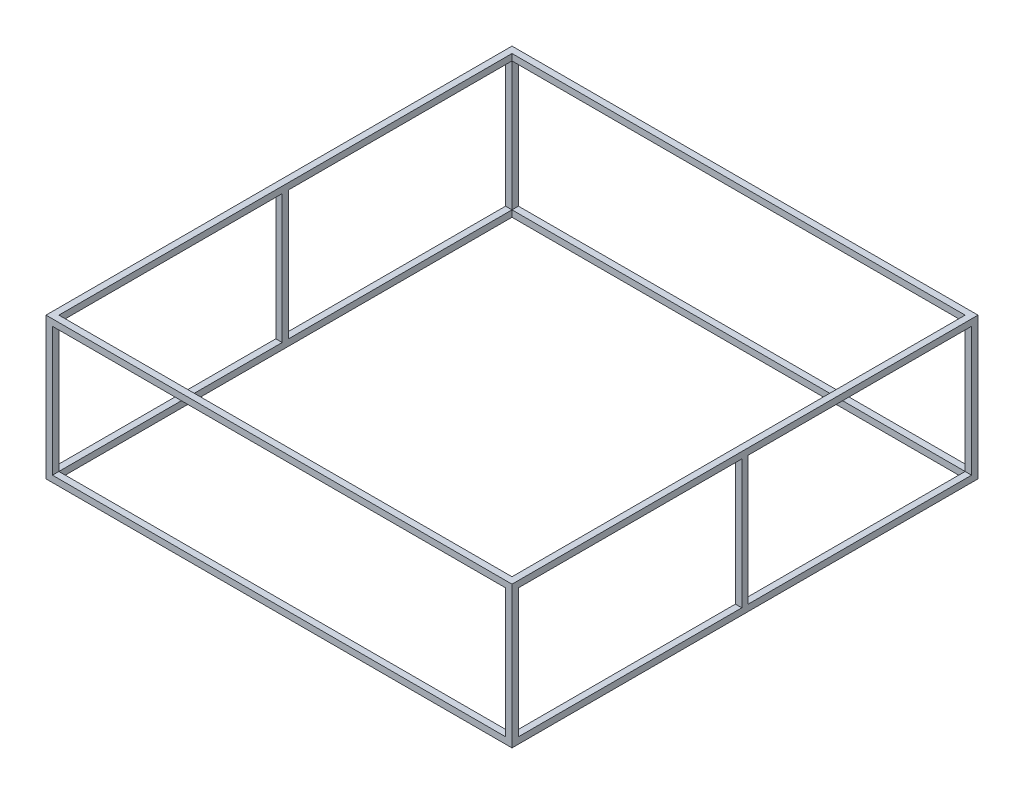
SolidWorks part; units mm, degrees
ref_plane "Front Plane" through (0, 0, 0) normal (0, 0, 1) x (1, 0, 0)
ref_plane "Top Plane" through (0, 0, 0) normal (0, 1, 0) x (1, 0, 0)
ref_plane "Right Plane" through (0, 0, 0) normal (1, 0, 0) x (0, 0, -1)
sketch "Sketch1" plane through (0, 0, 0) normal (0, 1, 0) x (1, 0, 0)
  line L0 (-559.125, 559.125) -> (-559.125, -559.125)
  line L1 (-575, 575) -> (575, 575)
  line L2 (-575, 575) -> (-575, -575)
  line L3 (-575, -575) -> (575, -575)
  line L4 (575, 575) -> (575, -575)
  line L5 (-575, 575) -> (575, -575) construction
  line L6 (-575, -575) -> (575, 575) construction
  line L7 (-559.125, -559.125) -> (559.125, -559.125)
  line L8 (559.125, 559.125) -> (559.125, -559.125)
  line L9 (-559.125, 559.125) -> (559.125, 559.125)
  point P0 (0, 0)
  dimension "D1" = 1150
  dimension "D2" = 1150
  dimension "D3" = 15.875
extrude "Boss-Extrude1" add sketch "Sketch1" along normal blind 15.875
sketch "Sketch2" plane through (0, 15.875, 0) normal (0, 1, 0) x (1, 0, 0)
  line L0 (-559.125, 559.125) -> (-559.125, -559.125) construction
  line L1 (-575, 575) -> (-559.125, 575)
  line L2 (-575, 575) -> (-575, 559.125)
  line L3 (-575, 559.125) -> (-559.125, 559.125)
  line L4 (-559.125, 575) -> (-559.125, 559.125)
  line L5 (559.125, 559.125) -> (-559.125, 559.125) construction
  line L6 (-575, 575) -> (-575, -575) construction
  line L7 (-575, -575) -> (-559.125, -575)
  line L8 (-575, -575) -> (-575, -559.125)
  line L9 (-575, -559.125) -> (-559.125, -559.125)
  line L10 (-559.125, -575) -> (-559.125, -559.125)
  line L11 (-575, 7.9375) -> (-559.125, 7.9375)
  line L12 (-575, 7.9375) -> (-575, -7.9375)
  line L13 (-575, -7.9375) -> (-559.125, -7.9375)
  line L14 (-559.125, 7.9375) -> (-559.125, -7.9375)
  point P21 (-575, 0)
  dimension "D1" = 15.875
extrude "Boss-Extrude2" add sketch "Sketch2" along normal blind 318.25
sketch "Sketch3" plane through (0, 334.125, 0) normal (0, 1, 0) x (1, 0, 0)
  line L4 (575, 575) -> (-575, 575)
  line L5 (575, -575) -> (575, 575)
  line L6 (-575, -575) -> (575, -575)
  line L7 (-575, 575) -> (-575, -575)
  line L8 (575, 575) -> (-575, 575)
  line L9 (575, -575) -> (575, 575)
  line L10 (-575, -575) -> (575, -575)
  line L11 (-575, 575) -> (-575, -575)
  line L12 (-559.125, 559.125) -> (-559.125, -559.125)
  line L13 (-559.125, -559.125) -> (559.125, -559.125)
  line L14 (559.125, -559.125) -> (559.125, 559.125)
  line L15 (559.125, 559.125) -> (-559.125, 559.125)
  line L16 (-559.125, 559.125) -> (-559.125, -559.125)
  line L17 (-559.125, -559.125) -> (559.125, -559.125)
  line L18 (559.125, -559.125) -> (559.125, 559.125)
  line L19 (559.125, 559.125) -> (-559.125, 559.125)
  dimension "D1" = 0
  dimension "D2" = 0
extrude "Boss-Extrude3" add sketch "Sketch3" along normal blind 15.875
mirror "Mirror1" about plane through (0, 0, 0) normal (1, 0, 0) of "Boss-Extrude2"
